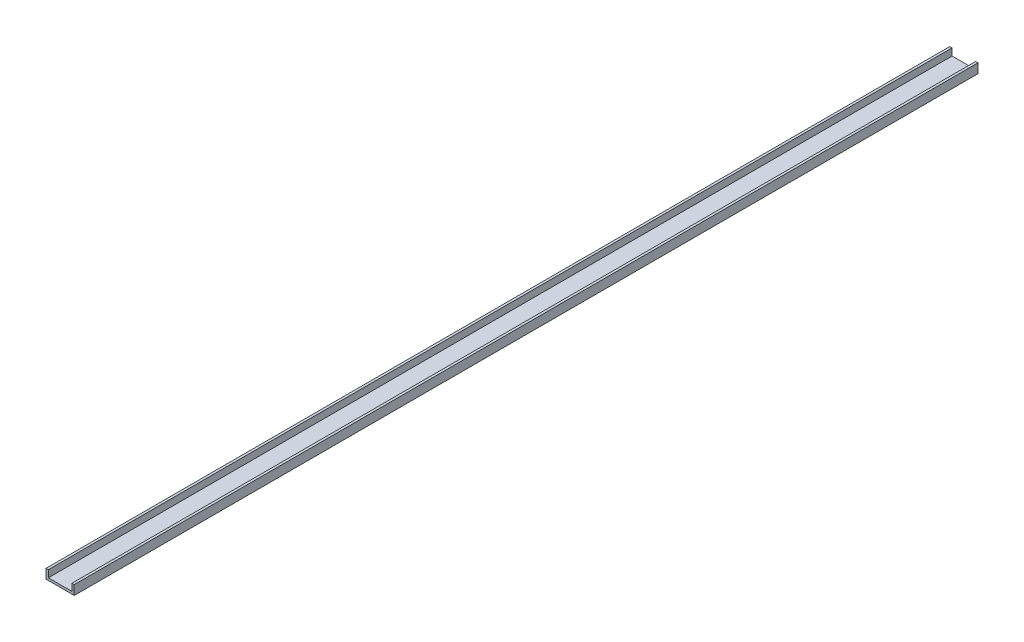
SolidWorks part; units mm, degrees
ref_plane "Front" through (0, 0, 0) normal (0, 0, 1) x (1, 0, 0)
ref_plane "Top" through (0, 0, 0) normal (0, 1, 0) x (1, 0, 0)
ref_plane "Right" through (0, 0, 0) normal (1, 0, 0) x (0, 0, -1)
sketch "Sketch1" plane through (0, 0, 0) normal (0, 0, 1) x (1, 0, 0)
  line L0 (3.175, 3.175) -> (3.175, 12.7)
  line L1 (0, 0) -> (38.1, 0)
  line L2 (0, 0) -> (0, 12.7)
  line L4 (38.1, 0) -> (38.1, 12.7)
  line L5 (3.175, 3.175) -> (34.925, 3.175)
  line L6 (34.925, 3.175) -> (34.925, 12.7)
  line L7 (0, 12.7) -> (3.175, 12.7)
  line L8 (38.1, 12.7) -> (34.925, 12.7)
  dimension "D1" = 12.7
  dimension "D2" = 38.1
  dimension "D3" = 3.175
extrude "f" add sketch "Sketch1" along normal blind 1219.2
